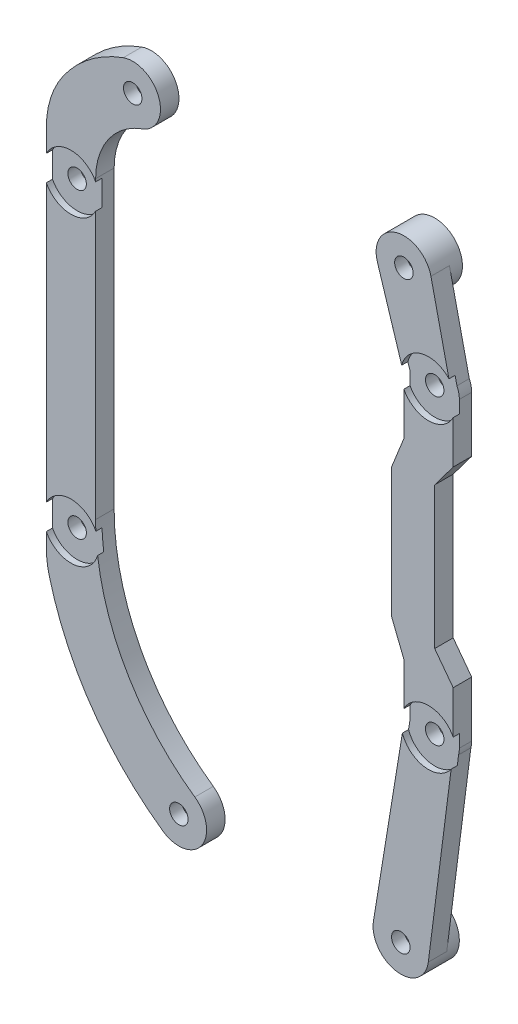
SolidWorks part; units mm, degrees
ref_plane "Front Plane" through (0, 0, 0) normal (0, 0, 1) x (1, 0, 0)
ref_plane "Top Plane" through (0, 0, 0) normal (0, 1, 0) x (1, 0, 0)
ref_plane "Right Plane" through (0, 0, 0) normal (1, 0, 0) x (0, 0, -1)
sketch "Sketch1" plane through (0, 0, 0) normal (0, 0, 1) x (1, 0, 0)
  line L0 (42, 25) -> (42, 16)
  line L1 (42, 16) -> (39, 12)
  line L2 (39, 12) -> (39, -11)
  line L3 (39, -11) -> (42, -15)
  line L4 (42, -15) -> (42, -24)
  line L5 (34, 25) -> (34, 16)
  line L6 (34, 16) -> (32, 11)
  line L7 (32, 11) -> (32, -10)
  line L8 (32, -10) -> (34, -15)
  line L9 (34, -15) -> (34, -24)
  line L10 (42, 16) -> (34, 16) construction
  line L11 (42, -15) -> (34, -15) construction
  line L12 (39, 12) -> (32, 11) construction
  line L13 (39, -11) -> (32, -10) construction
  line L14 (32, 0.5) -> (39, 0.5) construction
  circle A0 centre (38, 25) radius 4
  circle A1 centre (38, -24) radius 4
  circle A2 centre (38, -24) radius 1.5
  circle A3 centre (38, 25) radius 1.5
  dimension "D1" = 8
  dimension "D7" = 3
  dimension "D2" = 9
  dimension "D3" = 3
  dimension "D4" = 2
  dimension "D5" = 4
  dimension "D6" = 5
extrude "Boss-Extrude1" add sketch "Sketch1" along normal blind 3 contours A1 L4 L3 L2 L1 L0 A0 L5 L6 L7 L8 L9 | A0 A3 | A1 A2 region at (38, 21.1131, 0) region at (36.5126, 0.5, 0) region at (38, -27.8869, 0)
sketch "Sketch3" plane through (0, 0, 0) normal (0, 0, -1) x (-1, 0, 0)
  line L0 (20, 25) -> (20, -24) construction
  line L2 (16, -47.6521) -> (24, -47.6521)
  line L3 (16, -47.6521) -> (16, 48.6521)
  line L4 (16, 48.6521) -> (24, 48.6521)
  line L5 (24, -47.6521) -> (24, 48.6521)
  line L6 (16, -47.6521) -> (24, 48.6521) construction
  line L7 (16, 48.6521) -> (24, -47.6521) construction
  circle A0 centre (20, 25) radius 4
  circle A1 centre (20, -24) radius 4
  circle A2 centre (20, 25) radius 1.5
  circle A3 centre (20, -24) radius 1.5
  circle A4 centre (-38, 25) radius 1.5 construction
  point P10 (20, 0.5)
  dimension "D1" = 8
extrude "Boss-Extrude2" add sketch "Sketch3" against normal up to surface (3 mm away) separate body contours A0 L5 L4 L3 | A1 L5 A0 L3 | A0 A2 | A1 A3 | A1 L3 L2 L5 region at (-20, -37.3774, 0) region at (-20, 0.5, 0) region at (-20, -20.1131, 0) region at (-20, 38.3774, 0) region at (-20, 28.8869, 0) up to face at (37.1667, 0.5, 3)
sketch "Sketch4" plane through (0, 0, 3) normal (0, 0, 1) x (1, 0, 0)
  line L0 (38.3895, 40.9911) -> (42, 25)
  line L1 (29.7073, 38.65) -> (34, 25)
  line L2 (38, 25) -> (38, 15.9142) construction
  circle A0 centre (34, 40) radius 4.5
  circle A1 centre (34, 40) radius 1.5
  arc A2 (42, 25) -> (34, 25) centre (38, 25) ccw construction
  arc A3 (42, 25) -> (34, 25) centre (38, 25) ccw
  point P13 (35.5097, 39.0936)
  arc M8 (42, 25) -> (34, 25) centre (38, 25) ccw
  dimension "D1" = 9
  dimension "D2" = 3
  dimension "D3" = 15
  dimension "D4" = 4
extrude "Boss-Extrude3" add sketch "Sketch4" against normal up to surface (3 mm away) contours A0 L1 L0 M8 | A0 A1 region at (36.0637, 32.3875, 3) region at (38.3458, 40.4845, 3) up to face at (37.1667, 0.5, 0)
sketch "Sketch6" plane through (0, 0, 3) normal (0, 0, 1) x (1, 0, 0)
  line L0 (34, -24) -> (29.0588, -54.2751)
  line L1 (42, -24) -> (37.9637, -55.5707)
  circle A0 centre (33.5, -55) radius 1.5 construction
  circle A1 centre (33.5, -55) radius 1.5
  circle A2 centre (33.5, -55) radius 4.5
  arc A3 (34, -24) -> (42, -24) centre (38, -24) ccw construction
  arc A4 (34, -24) -> (42, -24) centre (38, -24) ccw
  arc M2 (34, -24) -> (42, -24) centre (38, -24) ccw
  dimension "D1" = 9
extrude "Boss-Extrude4" add sketch "Sketch6" against normal up to surface (3 mm away) contours A2 L1 L0 M2 | A2 A1 region at (35.7547, -39.5094, 3) region at (33.8533, -50.6416, 3) up to face at (36.9723, 7.527, 0)
sketch "Sketch7" plane through (0, 0, 3) normal (0, 0, 1) x (1, 0, 0)
  circle A0 centre (38, -24) radius 4.5
  circle A1 centre (38, 25) radius 4.5
  dimension "D1" = 9
extrude "Cut-Extrude1" cut sketch "Sketch7" against normal blind 1
sketch "Sketch8" plane through (0, 0, 0) normal (0, 0, 1) x (1, 0, 0)
  line L0 (33.7559, -25.4958) -> (29.0588, -54.2751) construction
  line L1 (34.0208, -51.8091) -> (30.997, -52.9535)
  line L2 (30.997, -52.9535) -> (30.4762, -56.1444)
  line L3 (30.4762, -56.1444) -> (32.9792, -58.1909)
  line L4 (32.9792, -58.1909) -> (36.003, -57.0465)
  line L5 (36.003, -57.0465) -> (36.5238, -53.8556)
  line L6 (36.5238, -53.8556) -> (34.0208, -51.8091)
  line L8 (38.3895, 40.9911) -> (41.3122, 28.0462) construction
  line L9 (34.7121, 36.8462) -> (37.0873, 39.0398)
  line L10 (37.0873, 39.0398) -> (36.3752, 42.1936)
  line L11 (36.3752, 42.1936) -> (33.2879, 43.1538)
  line L12 (33.2879, 43.1538) -> (30.9127, 40.9602)
  line L13 (30.9127, 40.9602) -> (31.6248, 37.8064)
  line L14 (31.6248, 37.8064) -> (34.7121, 36.8462)
  arc A0 (29.0588, -54.2751) -> (37.9637, -55.5707) centre (33.5, -55) ccw construction
  circle A1 centre (33.5, -55) radius 4.5
  circle A2 centre (33.5, -55) radius 2.8 construction
  arc A3 (38.3895, 40.9911) -> (29.7073, 38.65) centre (34, 40) ccw construction
  circle A4 centre (34, 40) radius 4.5
  circle A5 centre (34, 40) radius 2.8 construction
  dimension "D1" = 5.6
extrude "Boss-Extrude5" add sketch "Sketch8" against normal blind 2
sketch "Sketch9" plane through (0, 0, 0) normal (0, 0, 1) x (1, 0, 0)
  line L8 (31.6248, 37.8064) -> (34.7121, 36.8462)
  line L9 (30.9127, 40.9602) -> (31.6248, 37.8064)
  line L10 (33.2879, 43.1538) -> (30.9127, 40.9602)
  line L11 (36.3752, 42.1936) -> (33.2879, 43.1538)
  line L18 (37.0873, 39.0398) -> (36.3752, 42.1936)
  line L19 (34.7121, 36.8462) -> (37.0873, 39.0398)
  line L20 (31.6248, 37.8064) -> (34.7121, 36.8462)
  line L21 (30.9127, 40.9602) -> (31.6248, 37.8064)
  line L22 (33.2879, 43.1538) -> (30.9127, 40.9602)
  line L23 (36.3752, 42.1936) -> (33.2879, 43.1538)
  line L30 (37.0873, 39.0398) -> (36.3752, 42.1936)
  line L31 (34.7121, 36.8462) -> (37.0873, 39.0398)
  line L32 (36.5238, -53.8556) -> (34.0208, -51.8091)
  line L33 (36.003, -57.0465) -> (36.5238, -53.8556)
  line L34 (32.9792, -58.1909) -> (36.003, -57.0465)
  line L35 (30.4762, -56.1444) -> (32.9792, -58.1909)
  line L36 (30.997, -52.9535) -> (30.4762, -56.1444)
  line L37 (34.0208, -51.8091) -> (30.997, -52.9535)
  line L38 (36.5238, -53.8556) -> (34.0208, -51.8091)
  line L39 (36.003, -57.0465) -> (36.5238, -53.8556)
  line L40 (32.9792, -58.1909) -> (36.003, -57.0465)
  line L41 (30.4762, -56.1444) -> (32.9792, -58.1909)
  line L42 (30.997, -52.9535) -> (30.4762, -56.1444)
  line L43 (34.0208, -51.8091) -> (30.997, -52.9535)
  dimension "D1" = 0
  dimension "D2" = 0
extrude "Cut-Extrude2" cut sketch "Sketch9" along normal blind 1
sketch "Sketch11" plane through (0, 0, 0) normal (0, 0, -1) x (-1, 0, 0)
  line L0 (16, -47.6521) -> (16, 48.6521) construction
  line L1 (24, -47.6521) -> (24, 48.6521) construction
  line L2 (16, -47.6521) -> (24, -47.6521) construction
  line L3 (24, -47.6521) -> (24, 48.6521)
  line L4 (16, -47.6521) -> (24, -47.6521)
  line L5 (16, 48.6521) -> (24, 48.6521) construction
  line L6 (16, 48.6521) -> (24, 48.6521)
  line L7 (16, -47.6521) -> (16, 48.6521)
  circle A0 centre (9.9853, 42.5147) radius 1.5 construction
  circle A1 centre (9.9853, 42.5147) radius 1.5
  circle A2 centre (2.5, -55) radius 1.5 construction
  circle A3 centre (2.5, -55) radius 1.5
  circle A4 centre (2.5, -55) radius 4.5
  circle A5 centre (9.9853, 42.5147) radius 4.5
  arc A6 (-0.085, -51.3166) -> (16, -20.3773) centre (-21.7981, -20.3773) ccw
  arc A7 (5.085, -58.6834) -> (24, -30) centre (-21.7981, -20.3773) ccw
  arc A8 (11.52, 46.7449) -> (24, 33.8324) centre (4.5434, 27.5147) cw
  arc A9 (8.4506, 38.2845) -> (16, 27.5147) centre (4.5434, 27.5147) cw
  point P14 (16, -18.5025)
  point P24 (8.4929, 46.76)
  point P25 (24, 34.1624)
  point P26 (24, -28.0051)
  line M1 (16, 48.6521) -> (16, -47.6521)
  line M2 (16, -47.6521) -> (24, -47.6521)
  line M3 (24, -47.6521) -> (24, 48.6521)
  line M4 (24, 48.6521) -> (16, 48.6521)
  dimension "D1" = 9
  dimension "D2" = 15
  dimension "D3" = 25
extrude "Boss-Extrude6" add sketch "Sketch11" against normal up to surface (3 mm away) contours A5 A9 L7 A8 | A5 A1 | A4 A7 L7 A6 M2 | A4 A3 region at (-11.1205, -44.9713, 0) region at (1.0792, -57.5119, 0) region at (-14.3424, 38.0834, 0) region at (-13.5659, 45.0247, 0) up to face at (-20, 0.5, 3)
extrude "Cut-Extrude3" cut sketch "Sketch11<3>" against normal blind 10 contours A7 L4 M3 | A8 M1 M3 M4 region at (-21.6257, -42.4147, 0) region at (-20.804, 44.0025, 0)
sketch "Sketch11<3>" plane through (0, 0, 0) normal (0, 0, -1) x (-1, 0, 0) same geometry as "Sketch11"
fillet "Fillet1" radius 15 2 edges at (-24, 33.8324, 1.5) (-24, -30, 1.5)
sketch "Sketch13" plane through (0, 0, 3) normal (0, 0, 1) x (1, 0, 0)
  circle A0 centre (-20, 25) radius 4.5
  circle A1 centre (-20, -24) radius 4.5
  arc A2 (34, 22.9384) -> (42, 22.9384) centre (38, 25) ccw construction
extrude "Cut-Extrude4" cut sketch "Sketch13" against normal up to surface (1 mm away) up to face at (39.5, 25, 2)
sketch "Sketch14" plane through (0, 0, 0) normal (0, 0, 1) x (1, 0, 0)
  circle A0 centre (-9.9853, 42.5147) radius 2.8
  circle A1 centre (-2.5, -55) radius 2.8
  dimension "D1" = 5.6
extrude "Cut-Extrude5" cut sketch "Sketch14" along normal blind 1
